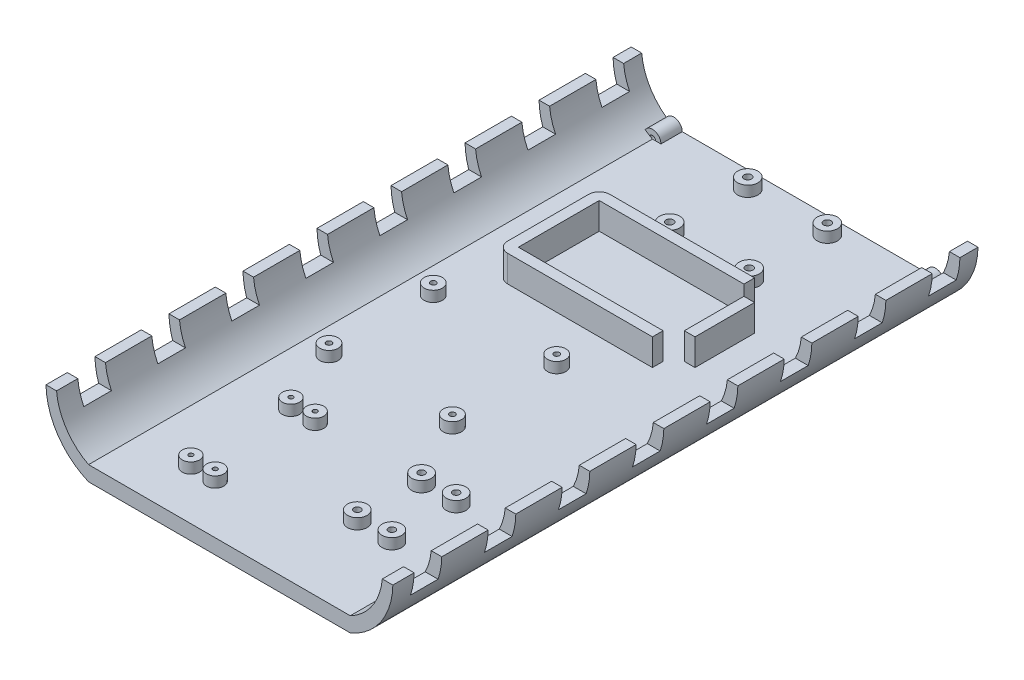
SolidWorks part; units mm, degrees
ref_plane "Front Plane" through (0, 0, 0) normal (0, 0, 1) x (1, 0, 0)
ref_plane "Top Plane" through (0, 0, 0) normal (0, 1, 0) x (1, 0, 0)
ref_plane "Right Plane" through (0, 0, 0) normal (1, 0, 0) x (0, 0, -1)
sketch "Sketch1" plane through (0, 0, 0) normal (0, 1, 0) x (1, 0, 0)
  line L1 (61.5, -137.5) -> (-61.5, -137.5)
  line L2 (61.5, -137.5) -> (61.5, 137.5)
  line L3 (61.5, 137.5) -> (-61.5, 137.5)
  line L4 (-61.5, -137.5) -> (-61.5, 137.5)
  line L5 (61.5, -137.5) -> (-61.5, 137.5) construction
  line L6 (61.5, 137.5) -> (-61.5, -137.5) construction
  point P0 (0, 0)
  dimension "D1" = 123
  dimension "D2" = 275
extrude "Boss-Extrude1" add sketch "Sketch1" along normal blind 7
sketch "Sketch2" plane through (0, 0, 137.5) normal (0, 0, 1) x (1, 0, 0)
  line L0 (-61.5, 7) -> (-76.548, 22.0465) construction
  line L1 (0, 0) -> (0, 29.496) construction
  line L2 (-61.5, 0) -> (-81.498, 19.996) construction
  line L3 (-81.498, 19.996) -> (-81.498, 29.496) construction
  line L4 (-81.498, 29.496) -> (-76.548, 29.496)
  line L5 (-76.548, 29.496) -> (-76.548, 22.0465) construction
  line L6 (-61.5, 0) -> (61.5, 0) construction
  line L7 (-61.5, 7) -> (-61.5, 0)
  line L8 (81.498, 29.496) -> (76.548, 29.496)
  line L9 (61.5, 7) -> (61.5, 0)
  arc A0 (-81.498, 29.496) -> (-61.5, 0) centre (-49.0031, 30) ccw
  arc A1 (-76.548, 29.496) -> (-61.5, 7) centre (-48.4655, 32) ccw
  arc A2 (81.498, 29.496) -> (61.5, 0) centre (49.0031, 30) cw
  arc A3 (76.548, 29.496) -> (61.5, 7) centre (48.4655, 32) cw
  dimension "D1" = 21.28
  dimension "D2" = 4.95
  dimension "D3" = 28.28
  dimension "D4" = 9.5
  dimension "D5" = 30
  dimension "D6" = 32
extrude "Boss-Extrude2" add sketch "Sketch2" against normal up to surface (275 mm away) contours A1 L7 A0 L4 | L8 A3 L9 A2 up to face at (0, 3.5, -137.5)
sketch "Sketch3" plane through (0, 0, 0) normal (1, 0, 0) x (0, 0, -1)
  line L0 (137.5, 29.496) -> (-137.5, 29.496) construction
  line L1 (-127.5, 29.496) -> (-114.5, 29.496)
  line L2 (-127.5, 29.496) -> (-127.5, 19.496)
  line L3 (-127.5, 19.496) -> (-114.5, 19.496)
  line L8 (-92.7143, 29.496) -> (-92.7143, 19.496)
  line L9 (-92.7143, 29.496) -> (-79.7143, 29.496)
  line L10 (-79.7143, 29.496) -> (-79.7143, 19.496)
  line L11 (-92.7143, 19.496) -> (-79.7143, 19.496)
  line L12 (-57.9286, 29.496) -> (-57.9286, 19.496)
  line L13 (-57.9286, 29.496) -> (-44.9286, 29.496)
  line L14 (-44.9286, 29.496) -> (-44.9286, 19.496)
  line L15 (-57.9286, 19.496) -> (-44.9286, 19.496)
  line L16 (-23.1429, 29.496) -> (-23.1429, 19.496)
  line L17 (-23.1429, 29.496) -> (-10.1429, 29.496)
  line L18 (-10.1429, 29.496) -> (-10.1429, 19.496)
  line L19 (-23.1429, 19.496) -> (-10.1429, 19.496)
  line L20 (11.6429, 29.496) -> (11.6429, 19.496)
  line L21 (11.6429, 29.496) -> (24.6429, 29.496)
  line L22 (24.6429, 29.496) -> (24.6429, 19.496)
  line L23 (11.6429, 19.496) -> (24.6429, 19.496)
  line L24 (46.4286, 29.496) -> (46.4286, 19.496)
  line L25 (46.4286, 29.496) -> (59.4286, 29.496)
  line L26 (59.4286, 29.496) -> (59.4286, 19.496)
  line L27 (46.4286, 19.496) -> (59.4286, 19.496)
  line L28 (81.2143, 29.496) -> (81.2143, 19.496)
  line L29 (81.2143, 29.496) -> (94.2143, 29.496)
  line L30 (94.2143, 29.496) -> (94.2143, 19.496)
  line L31 (81.2143, 19.496) -> (94.2143, 19.496)
  line L32 (116, 29.496) -> (116, 19.496)
  line L33 (116, 29.496) -> (129, 29.496)
  line L35 (116, 19.496) -> (129, 19.496)
  line L37 (137.5, 29.496) -> (-137.5, 29.496) construction
  line L38 (-127.5, 38.996) -> (-127.5, 29.496) construction
  line L39 (-114.5, 29.496) -> (-114.5, 19.496)
  line L40 (-114.5, 38.996) -> (-114.5, 29.496) construction
  line L41 (129, 29.496) -> (129, 19.496)
  line L42 (129, 38.996) -> (129, 29.496) construction
  dimension "D1" = 10
  dimension "D2" = 8
extrude "Cut-Extrude1" cut sketch "Sketch3" against normal through all both and the other way through all contours L2 L1 L39 L3 | L8 L11 L10 L9 | L12 L15 L14 L13 | L16 L19 L18 L17 | L20 L23 L22 L21 | L24 L27 L26 L25 | L28 L31 L30 L29 | L32 L35 L41 L33
sketch "Sketch4" plane through (0, 0, -137.5) normal (0, 0, -1) x (-1, 0, 0)
  line L0 (0, 0) -> (0, 7) construction
  line L1 (-61.5, 7) -> (61.5, 7) construction
  circle A0 centre (61.5, 7) radius 1.5
  circle A1 centre (61.5, 7) radius 4
  circle A2 centre (-61.5, 7) radius 4
  circle A3 centre (-61.5, 7) radius 1.5
  dimension "D1" = 3
  dimension "D2" = 8
extrude "Boss-Extrude3" add sketch "Sketch4" against normal blind 10
sketch "Sketch5" plane through (0, 0, -137.5) normal (0, 0, -1) x (-1, 0, 0)
  circle A0 centre (61.5, 7) radius 1.5
  circle A1 centre (-61.5, 7) radius 1.5
  dimension "D1" = 3
  dimension "D2" = 3
extrude "Cut-Extrude2" cut sketch "Sketch5" against normal blind 10
sketch "Sketch8" plane through (0, 0, 0) normal (0, -1, 0) x (1, 0, 0)
  line L0 (-0.0256, 57.4884) -> (-0.0256, -44.5116) construction
  line L1 (-50.0256, -29.5701) -> (49.9744, -29.5701) construction
  arc A0 (-50.0256, -29.5701) -> (-0.0256, 57.4884) centre (39.7518, -23.2442) cw
  arc A1 (-0.0256, 38.2605) -> (-32.6817, -19.623) centre (42.2063, -23.719) ccw
  arc A2 (-0.0256, 38.2605) -> (32.6306, -19.623) centre (-42.2575, -23.719) cw
  arc A3 (49.9744, -29.5701) -> (-0.0256, 57.4884) centre (-39.803, -23.2442) ccw
  arc A4 (-50.0256, -29.5701) -> (49.9744, -29.5701) centre (-0.0256, 45.263) ccw
  arc A5 (-32.6817, -19.623) -> (32.6306, -19.623) centre (-0.0256, 47.763) ccw
  dimension "D3" = 90
  dimension "D4" = 75
  dimension "D9" = 90
  dimension "D1" = 100
  dimension "D2" = 102
  dimension "D5" = 2.5
  dimension "D6" = 87.0586
  dimension "D7" = 57.8835
  dimension "D8" = 82.7721
  dimension "D10" = 2.5
extrude "Cut-Extrude3" cut sketch "Sketch8" against normal blind 3 contours A0 A3 A4 | A1 A5 A2
sketch "Sketch9" plane through (0, 0, 0) normal (0, -1, 0) x (1, 0, 0)
  line L0 (-50.0889, -28.6883) -> (38.178, 22.4605) construction
  line L1 (11.8277, 51.2634) -> (5.8441, 51.7067)
  line L2 (-0.0889, 58.3703) -> (-0.0889, -43.8551) construction
  line L3 (-49.9678, -14.9758) -> (-47.3599, -20.3794)
  line L4 (-44.0439, -15.9285) -> (-49.9678, -14.9758)
  line L5 (-44.0439, -15.9285) -> (-45.6972, -18.1477) construction
  line L6 (-47.3599, -20.3794) -> (-48.837, -22.3621) construction
  line L7 (-47.3599, -20.3794) -> (-50.3006, -19.7443)
  line L8 (-45.4283, -18.6228) -> (-42.7418, -23.3693)
  line L9 (-42.7418, -23.3693) -> (-39.7214, -18.6859) construction
  line L10 (-39.7214, -18.6859) -> (-45.1135, -18.2003)
  line L11 (-49.905, -24.6318) -> (-48.5689, -22.8383)
  line L12 (-42.7418, -23.3693) -> (-43.8348, -25.0642) construction
  line L13 (-45.6931, -27.9456) -> (-48.5689, -22.8383)
  line L14 (-48.2824, -22.4538) -> (-42.7418, -23.3693)
  line L15 (-48.5689, -22.8383) -> (-48.837, -22.3621) construction
  line L16 (-48.837, -22.3621) -> (-50.3056, -24.3333) construction
  line L17 (-48.837, -22.3621) -> (-48.2824, -22.4538) construction
  line L18 (-48.2824, -22.4538) -> (-45.4283, -18.6228)
  line L19 (-48.5689, -22.8383) -> (-48.2824, -22.4538) construction
  line L20 (-45.6972, -18.1477) -> (-47.3599, -20.3794) construction
  line L21 (-45.1135, -18.2003) -> (-45.6972, -18.1477) construction
  line L22 (-45.6972, -18.1477) -> (-45.4283, -18.6228) construction
  line L23 (-45.1135, -18.2003) -> (-43.6305, -16.2097)
  line L24 (-45.4283, -18.6228) -> (-45.1135, -18.2003) construction
  line L25 (-39.2905, -18.9395) -> (-40.7869, -21.2598)
  line L26 (-43.8348, -25.0642) -> (-45.6931, -27.9456) construction
  line L27 (-50.3056, -24.3333) -> (-49.905, -24.6318)
  line L28 (-35.4051, -21.3791) -> (-40.7869, -21.2598)
  line L29 (-41.4061, -21.2461) -> (-41.389, -21.2717)
  line L30 (-36.1561, -23.7758) -> (-34.9595, -21.6011)
  line L31 (-30.7483, -23.5189) -> (-36.1561, -23.7758)
  line L32 (-36.4101, -24.2375) -> (-33.0992, -28.5716)
  line L33 (-30.2812, -23.6993) -> (-31.4515, -26.2144)
  line L34 (-38.713, -28.423) -> (-33.0992, -28.5716)
  line L35 (-38.713, -28.423) -> (-36.4101, -24.2375)
  line L36 (-38.0831, -26.2419) -> (-43.725, -25.8157)
  line L37 (-43.8692, -26.0393) -> (-40.4599, -30.5618)
  line L38 (-40.4599, -30.5618) -> (-40.0223, -30.8026)
  line L39 (-40.0223, -30.8026) -> (-38.9442, -28.8432)
  line L40 (-35.3964, -33.5088) -> (-38.9442, -28.8432)
  line L41 (-2.0353, 58.2366) -> (11.9562, -43.0268) construction
  line L42 (-26.1016, -25.5957) -> (-31.4515, -26.2144)
  line L43 (-31.6852, -26.7168) -> (-28.0912, -30.7796)
  line L44 (-26.5199, -28.0729) -> (-25.6322, -25.7548)
  line L45 (-21.1981, -27.0783) -> (-26.5199, -28.0729)
  line L46 (-26.7083, -28.565) -> (-22.8354, -32.4051)
  line L47 (-20.7105, -27.1924) -> (-21.5257, -29.8447)
  line L48 (-28.4166, -33.0263) -> (-22.8354, -32.4051)
  line L49 (-28.4166, -33.0263) -> (-26.7083, -28.565)
  line L50 (-28.0912, -30.7796) -> (-33.7384, -31.1296)
  line L51 (-33.8501, -31.3698) -> (-29.8544, -35.3841)
  line L52 (-29.8544, -35.3841) -> (-29.3879, -35.5627)
  line L53 (-29.3879, -35.5627) -> (-28.5881, -33.4742)
  line L54 (-24.4352, -37.6103) -> (-28.5881, -33.4742)
  line L55 (-3.945, 57.8378) -> (23.7745, -40.5577) construction
  line L56 (-16.3086, -28.4989) -> (-21.5257, -29.8447)
  line L57 (-21.6885, -30.3743) -> (-17.5723, -33.9069)
  line L58 (-16.3862, -31.0107) -> (-15.8242, -28.5929)
  line L59 (-11.2507, -29.297) -> (-16.3862, -31.0107)
  line L60 (-16.5055, -31.5239) -> (-12.1434, -34.7978)
  line L61 (-10.752, -29.3429) -> (-11.1966, -32.0822)
  line L62 (-17.5872, -36.1771) -> (-12.1434, -34.7978)
  line L63 (-17.5872, -36.1771) -> (-16.5055, -31.5239)
  line L64 (-17.5723, -33.9069) -> (-23.1184, -35.0265)
  line L65 (-23.196, -35.2791) -> (-18.6887, -38.7094)
  line L66 (-18.6887, -38.7094) -> (-18.2021, -38.8225)
  line L67 (-18.2021, -38.8225) -> (-17.6957, -36.6442)
  line L68 (-13.0157, -40.173) -> (-17.6957, -36.6442)
  line L69 (-5.7815, 57.1796) -> (32.331, -30.0564) construction
  line L70 (-6.2106, -30.0342) -> (-11.1966, -32.0822)
  line L71 (-11.2853, -32.6291) -> (-6.7243, -35.5651)
  line L72 (-5.9458, -32.5338) -> (-5.72, -30.0619)
  line L73 (-1.0931, -30.1334) -> (-5.9458, -32.5338)
  line L74 (-5.9937, -33.0586) -> (-1.2246, -35.7046)
  line L75 (-0.5929, -30.1105) -> (-0.6583, -32.885)
  line L76 (-6.4283, -37.816) -> (-1.2246, -35.7046)
  line L77 (-6.4283, -37.816) -> (-5.9937, -33.0586)
  line L78 (-6.7243, -35.5651) -> (-12.065, -37.4333)
  line L79 (-12.1073, -37.6937) -> (-7.1729, -40.4753)
  line L80 (-7.1729, -40.4753) -> (-6.6754, -40.5207)
  line L81 (-6.6754, -40.5207) -> (-6.472, -38.2935)
  line L82 (-1.353, -41.1486) -> (-6.472, -38.2935)
  line L83 (10.3335, -40.5187) -> (10.8273, -40.4403)
  line L84 (4.0023, -30.1727) -> (-0.6583, -32.885)
  line L85 (-0.6714, -33.4389) -> (4.2485, -35.723)
  line L86 (4.6048, -32.6136) -> (4.4902, -30.1341)
  line L87 (9.0833, -29.5716) -> (4.6048, -32.6136)
  line L88 (4.6292, -33.14) -> (9.7156, -35.1084)
  line L89 (9.5757, -29.4807) -> (9.8906, -32.2378)
  line L90 (4.8498, -37.9121) -> (9.7156, -35.1084)
  line L91 (4.8498, -37.9121) -> (4.6292, -33.14)
  line L92 (4.2485, -35.723) -> (-0.7862, -38.3046)
  line L93 (-0.7924, -38.5682) -> (4.4762, -40.6483)
  line L94 (4.4762, -40.6483) -> (4.9752, -40.6252)
  line L95 (4.9752, -40.6252) -> (4.8719, -38.3912)
  line L96 (10.3335, -40.5187) -> (4.8719, -38.3912)
  line L97 (-1.353, -41.1486) -> (-0.8531, -41.1382)
  line L98 (14.1377, -28.912) -> (9.8906, -32.2378)
  line L99 (9.9535, -32.7883) -> (15.1397, -34.3776)
  line L100 (15.0671, -31.2487) -> (14.6142, -28.8082)
  line L101 (19.087, -27.6224) -> (15.0671, -31.2487)
  line L102 (15.1632, -31.7668) -> (20.4712, -33.0205)
  line L103 (19.5625, -27.4655) -> (20.2517, -30.153)
  line L104 (16.0349, -36.4638) -> (20.4712, -33.0205)
  line L105 (16.0349, -36.4638) -> (15.1632, -31.7668)
  line L106 (15.1397, -34.3776) -> (10.5057, -37.6239)
  line L107 (10.5356, -37.8861) -> (16.0394, -39.2254)
  line L108 (16.0394, -39.2254) -> (16.5305, -39.1342)
  line L109 (16.5305, -39.1342) -> (16.1224, -36.9353)
  line L110 (21.8238, -38.2953) -> (16.1224, -36.9353)
  line L111 (-13.0157, -40.173) -> (-12.5191, -40.2312)
  line L112 (24.0048, -26.2759) -> (20.2517, -30.153)
  line L113 (20.3893, -30.6897) -> (25.7442, -31.5541)
  line L114 (25.2441, -28.4646) -> (24.4614, -26.1091)
  line L115 (28.7298, -24.3222) -> (25.2441, -28.4646)
  line L116 (25.4102, -28.9647) -> (30.8398, -29.4801)
  line L117 (29.1797, -24.1026) -> (30.2299, -26.6696)
  line L118 (26.9166, -33.4982) -> (30.8398, -29.4801)
  line L119 (26.9166, -33.4982) -> (25.4102, -28.9647)
  line L120 (25.7442, -31.5541) -> (21.5982, -35.4042)
  line L121 (21.6639, -35.6604) -> (27.2989, -36.2332)
  line L122 (27.2989, -36.2332) -> (27.773, -36.0756)
  line L123 (27.773, -36.0756) -> (27.0678, -33.9533)
  line L124 (31.7808, -34.4113) -> (27.0678, -33.9533)
  line L125 (-24.4352, -37.6103) -> (-23.9513, -37.7364)
  line L126 (32.6776, -23.3255) -> (30.2299, -26.6696)
  line L127 (30.4397, -27.1824) -> (32.5504, -27.2305)
  line L128 (-35.3964, -33.5088) -> (-34.9346, -33.7006)
  line L129 (21.8238, -38.2953) -> (22.3024, -38.1506)
  line L130 (28.7298, -24.3222) -> (29.1797, -24.1026)
  line L131 (24.0048, -26.2759) -> (24.4614, -26.1091)
  line L132 (19.087, -27.6224) -> (19.5625, -27.4655)
  line L133 (14.1377, -28.912) -> (14.6142, -28.8082)
  line L134 (9.0833, -29.5716) -> (9.5757, -29.4807)
  line L135 (4.0023, -30.1727) -> (4.4902, -30.1341)
  line L136 (-1.0931, -30.1334) -> (-0.5929, -30.1105)
  line L137 (-6.2106, -30.0342) -> (-5.72, -30.0619)
  line L138 (-11.2507, -29.297) -> (-10.752, -29.3429)
  line L139 (-16.3086, -28.4989) -> (-15.8242, -28.5929)
  line L140 (-21.1981, -27.0783) -> (-20.7105, -27.1924)
  line L141 (-26.1016, -25.5957) -> (-25.6322, -25.7548)
  line L142 (-30.7483, -23.5189) -> (-30.2812, -23.6993)
  line L143 (-35.4051, -21.3791) -> (-34.9595, -21.6011)
  line L144 (8.0407, 46.6095) -> (11.8277, 51.2634)
  line L145 (5.8441, 51.7067) -> (7.8645, 53.9359)
  line L146 (6.3995, 49.1556) -> (0.9457, 49.2022)
  line L147 (3.4915, 44.2448) -> (6.6081, 48.6717)
  line L148 (3.434, 56.037) -> (4.3191, 53.9832)
  line L149 (-1.5418, 54.0463) -> (4.3191, 53.9832)
  line L150 (4.5089, 53.5428) -> (0.9457, 49.2022)
  line L151 (4.5089, 53.5428) -> (6.3995, 49.1556)
  line L152 (6.6081, 48.6717) -> (7.5905, 46.3921)
  line L153 (3.0564, 43.9984) -> (1.7951, 46.4545)
  line L154 (3.8928, 56.2347) -> (3.434, 56.037)
  line L155 (-0.999, 41.8534) -> (1.7951, 46.4545)
  line L156 (2.1166, 46.9839) -> (2.0859, 46.9819)
  line L157 (-2.6992, 43.7021) -> (-1.4141, 41.5785)
  line L158 (-5.1806, 38.8904) -> (-2.6992, 43.7021)
  line L159 (-2.972, 44.1529) -> (-8.3809, 43.4526)
  line L160 (-5.5704, 38.5761) -> (-7.1634, 40.8471)
  line L161 (-5.4453, 48.24) -> (-8.3809, 43.4526)
  line L162 (-5.4453, 48.24) -> (-2.972, 44.1529)
  line L163 (-3.8714, 46.604) -> (-0.6813, 51.2769)
  line L164 (-0.8028, 51.5136) -> (-6.4241, 50.8223)
  line L165 (-6.4241, 50.8223) -> (-6.8515, 50.5637)
  line L166 (-6.8515, 50.5637) -> (-5.6936, 48.6503)
  line L167 (-11.508, 47.9106) -> (-5.6936, 48.6503)
  line L168 (-9.3025, 35.9046) -> (-7.1634, 40.8471)
  line L169 (-7.4816, 41.3007) -> (-12.797, 40.2196)
  line L170 (-11.2387, 37.5054) -> (-9.675, 35.5777)
  line L171 (-13.0382, 32.3994) -> (-11.2387, 37.5054)
  line L172 (-11.5706, 37.9147) -> (-16.8328, 36.4807)
  line L173 (-13.3808, 32.0341) -> (-15.2701, 34.0663)
  line L174 (-14.5801, 41.6248) -> (-16.8328, 36.4807)
  line L175 (-14.5801, 41.6248) -> (-11.5706, 37.9147)
  line L176 (-12.797, 40.2196) -> (-10.2766, 45.2852)
  line L177 (-10.4287, 45.5021) -> (-15.9031, 44.0488)
  line L178 (-43.8692, -26.0393) -> (-45.2625, -28.1997)
  line L179 (-43.725, -25.8157) -> (-43.8692, -26.0393) construction
  line L180 (-43.725, -25.8157) -> (-44.0566, -25.7907) construction
  line L181 (-44.0566, -25.7907) -> (-43.8692, -26.0393) construction
  line L182 (-41.373, -21.2469) -> (-41.4061, -21.2461)
  line L183 (-40.7869, -21.2598) -> (-41.373, -21.2469) construction
  line L184 (-41.0872, -21.7255) -> (-43.725, -25.8157)
  line L185 (-40.7869, -21.2598) -> (-41.0872, -21.7255) construction
  line L186 (-41.0872, -21.7255) -> (-38.0831, -26.2419)
  line L187 (-41.389, -21.2717) -> (-41.0872, -21.7255) construction
  line L188 (-31.4515, -26.2144) -> (-32.0667, -26.2856) construction
  line L189 (-32.0667, -26.2856) -> (-31.6852, -26.7168) construction
  line L190 (-31.6852, -26.7168) -> (-33.7384, -31.1296)
  line L191 (-31.4515, -26.2144) -> (-31.6852, -26.7168) construction
  line L192 (-34.0688, -31.15) -> (-33.8501, -31.3698) construction
  line L193 (-33.7384, -31.1296) -> (-34.0688, -31.15) construction
  line L194 (-33.8501, -31.3698) -> (-34.9346, -33.7006)
  line L195 (-33.7384, -31.1296) -> (-33.8501, -31.3698) construction
  line L196 (-23.442, -35.0919) -> (-23.196, -35.2791) construction
  line L197 (-23.196, -35.2791) -> (-23.9513, -37.7364)
  line L198 (-23.1184, -35.0265) -> (-23.196, -35.2791) construction
  line L199 (-23.1184, -35.0265) -> (-23.442, -35.0919) construction
  line L200 (-22.1254, -29.9993) -> (-21.6885, -30.3743) construction
  line L201 (-21.5257, -29.8447) -> (-22.1254, -29.9993) construction
  line L202 (-21.6885, -30.3743) -> (-23.1184, -35.0265)
  line L203 (-21.5257, -29.8447) -> (-21.6885, -30.3743) construction
  line L204 (-12.3761, -37.5421) -> (-12.1073, -37.6937) construction
  line L205 (-12.1073, -37.6937) -> (-12.5191, -40.2312)
  line L206 (-12.065, -37.4333) -> (-12.1073, -37.6937) construction
  line L207 (-12.065, -37.4333) -> (-12.3761, -37.5421) construction
  line L208 (-0.0899, 44.1495) -> (0.1587, 48.5959) construction
  line L209 (-11.7694, -32.3175) -> (-11.2853, -32.6291) construction
  line L210 (-11.1966, -32.0822) -> (-11.7694, -32.3175) construction
  line L211 (-11.2853, -32.6291) -> (-12.065, -37.4333)
  line L212 (-11.1966, -32.0822) -> (-11.2853, -32.6291) construction
  line L213 (-0.6583, -32.885) -> (-1.1936, -33.1965) construction
  line L214 (-1.1936, -33.1965) -> (-0.6714, -33.4389) construction
  line L215 (-0.6714, -33.4389) -> (-0.7862, -38.3046)
  line L216 (-0.6583, -32.885) -> (-0.6714, -33.4389) construction
  line L217 (-0.7862, -38.3046) -> (-1.0794, -38.4549) construction
  line L218 (-1.0794, -38.4549) -> (-0.7924, -38.5682) construction
  line L219 (-0.7924, -38.5682) -> (-0.8531, -41.1382)
  line L220 (-0.7862, -38.3046) -> (-0.7924, -38.5682) construction
  line L221 (9.8906, -32.2378) -> (9.403, -32.6196) construction
  line L222 (9.9535, -32.7883) -> (10.5057, -37.6239)
  line L223 (9.8906, -32.2378) -> (9.9535, -32.7883) construction
  line L224 (9.403, -32.6196) -> (9.9535, -32.7883) construction
  line L225 (10.5057, -37.6239) -> (10.2356, -37.8131) construction
  line L226 (10.2356, -37.8131) -> (10.5356, -37.8861) construction
  line L227 (10.5356, -37.8861) -> (10.8273, -40.4403)
  line L228 (10.5057, -37.6239) -> (10.5356, -37.8861) construction
  line L229 (21.356, -35.6291) -> (21.6639, -35.6604) construction
  line L230 (21.5982, -35.4042) -> (21.356, -35.6291) construction
  line L231 (21.6639, -35.6604) -> (22.3024, -38.1506)
  line L232 (21.5982, -35.4042) -> (21.6639, -35.6604) construction
  line L233 (20.2517, -30.153) -> (19.8209, -30.5979) construction
  line L234 (19.8209, -30.5979) -> (20.3893, -30.6897) construction
  line L235 (20.3893, -30.6897) -> (21.5982, -35.4042)
  line L236 (20.2517, -30.153) -> (20.3893, -30.6897) construction
  line L237 (30.2299, -26.6696) -> (29.8641, -27.1693) construction
  line L238 (30.4397, -27.1824) -> (32.1836, -31.4455)
  line L239 (30.2299, -26.6696) -> (30.4397, -27.1824) construction
  line L240 (29.8641, -27.1693) -> (30.4397, -27.1824) construction
  line L241 (-15.9031, 44.0488) -> (-16.291, 43.7341)
  line L242 (-16.291, 43.7341) -> (-14.8822, 41.9972)
  line L243 (-20.5406, 40.4687) -> (-14.8822, 41.9972)
  line L244 (-16.7133, 28.8752) -> (-15.2701, 34.0663)
  line L245 (-15.6474, 34.4721) -> (-20.7649, 32.6736)
  line L246 (-18.8497, 30.1983) -> (-17.0369, 28.5027)
  line L247 (-19.9334, 24.894) -> (-18.8497, 30.1983)
  line L248 (-19.2345, 30.5582) -> (-24.2509, 28.4175)
  line L249 (-20.2224, 24.485) -> (-22.3725, 26.2397)
  line L250 (-22.7235, 33.8216) -> (-24.2509, 28.4175)
  line L251 (-22.7235, 33.8216) -> (-19.2345, 30.5582)
  line L252 (-20.7649, 32.6736) -> (-18.9614, 38.0365)
  line L253 (-19.1413, 38.23) -> (-24.3658, 36.0417)
  line L254 (-24.3658, 36.0417) -> (-24.707, 35.6769)
  line L255 (-24.707, 35.6769) -> (-23.0737, 34.1491)
  line L256 (-28.4697, 31.8605) -> (-23.0737, 34.1491)
  line L257 (-23.0918, 20.8977) -> (-22.3725, 26.2397)
  line L258 (-22.8018, 26.59) -> (-27.6249, 24.1081)
  line L259 (-25.389, 21.9182) -> (-23.3612, 20.4867)
  line L260 (-25.7365, 16.5155) -> (-25.389, 21.9182)
  line L261 (-25.8195, 22.2221) -> (-30.4956, 19.4149)
  line L262 (-25.9668, 16.0708) -> (-28.3368, 17.5147)
  line L263 (-29.7222, 24.9772) -> (-30.4956, 19.4149)
  line L264 (-29.7222, 24.9772) -> (-25.8195, 22.2221)
  line L265 (-27.6249, 24.1081) -> (-26.5725, 29.6674)
  line L266 (-26.7768, 29.8341) -> (-31.6529, 26.9516)
  line L267 (-31.6529, 26.9516) -> (-31.941, 26.5435)
  line L268 (-31.941, 26.5435) -> (-30.114, 25.2538)
  line L269 (-35.146, 22.2481) -> (-30.114, 25.2538)
  line L270 (-40.4437, 11.8124) -> (-40.6228, 11.3455)
  line L271 (-28.3182, 12.1224) -> (-28.3368, 17.5147)
  line L272 (-28.81, 17.803) -> (-33.2481, 14.6843)
  line L273 (-30.7334, 12.821) -> (-28.5288, 11.6805)
  line L274 (-30.3382, 7.4216) -> (-30.7334, 12.821)
  line L275 (-31.2015, 13.0631) -> (-35.4494, 9.6424)
  line L276 (-30.5057, 6.9497) -> (-33.0508, 8.0555)
  line L277 (-35.4445, 15.2581) -> (-35.4494, 9.6424)
  line L278 (-35.4445, 15.2581) -> (-31.2015, 13.0631)
  line L279 (-33.2481, 14.6843) -> (-32.9664, 20.3353)
  line L280 (-33.1916, 20.4724) -> (-37.6273, 16.9498)
  line L281 (-37.6273, 16.9498) -> (-37.8569, 16.5061)
  line L282 (-37.8569, 16.5061) -> (-35.8705, 15.4785)
  line L283 (-40.4437, 11.8124) -> (-35.8705, 15.4785)
  line L284 (-35.146, 22.2481) -> (-35.387, 21.81)
  line L285 (-32.2941, 2.7145) -> (-33.0508, 8.0555)
  line L286 (-33.559, 8.2763) -> (-37.5285, 4.5795)
  line L287 (-34.7825, 3.078) -> (-32.4425, 2.2499)
  line L288 (-33.6519, -2.2166) -> (-34.7825, 3.078)
  line L289 (-35.2792, 3.2537) -> (-39.019, -0.7162)
  line L290 (-33.7538, -2.7068) -> (-36.4258, -1.9599)
  line L291 (-39.7828, 4.8473) -> (-39.019, -0.7162)
  line L292 (-39.7828, 4.8473) -> (-35.2792, 3.2537)
  line L293 (-37.5285, 4.5795) -> (-38.0229, 10.2159)
  line L294 (-38.2649, 10.321) -> (-42.1766, 6.2243)
  line L295 (-42.1766, 6.2243) -> (-42.3432, 5.7534)
  line L296 (-42.3432, 5.7534) -> (-40.2349, 5.0073)
  line L297 (-44.2634, 0.7498) -> (-40.2349, 5.0073)
  line L298 (-28.4697, 31.8605) -> (-28.7685, 31.4596)
  line L299 (-34.9447, -7.1487) -> (-36.4258, -1.9599)
  line L300 (-36.9594, -1.8107) -> (-40.3856, -6.016)
  line L301 (-37.4599, -7.1276) -> (-35.0286, -7.6275)
  line L302 (-35.6154, -12.2176) -> (-37.4599, -7.1276)
  line L303 (-37.976, -7.0215) -> (-41.1372, -11.4659)
  line L304 (-35.6501, -12.717) -> (-38.3983, -12.3429)
  line L305 (-42.6554, -6.0592) -> (-41.1372, -11.4659)
  line L306 (-42.6554, -6.0592) -> (-37.976, -7.0215)
  line L307 (-40.3856, -6.016) -> (-41.6468, -0.5004)
  line L308 (-41.9015, -0.4292) -> (-45.2151, -5.0229)
  line L309 (-45.2151, -5.0229) -> (-45.3157, -5.5122)
  line L310 (-45.3157, -5.5122) -> (-43.1251, -5.9627)
  line L311 (-45.8782, -9.8152) -> (-43.1251, -5.9627)
  line L312 (-20.5406, 40.4687) -> (-20.8918, 40.1127)
  line L313 (-36.726, -16.1348) -> (-38.3983, -12.3429)
  line L314 (-38.9473, -12.2682) -> (-40.0443, -14.0722)
  line L315 (-11.508, 47.9106) -> (-11.905, 47.6067)
  line L316 (-44.2634, 0.7498) -> (-44.3774, 0.263)
  line L317 (-35.6154, -12.2176) -> (-35.6501, -12.717)
  line L318 (-34.9447, -7.1487) -> (-35.0286, -7.6275)
  line L319 (-33.6519, -2.2166) -> (-33.7538, -2.7068)
  line L320 (-32.2941, 2.7145) -> (-32.4425, 2.2499)
  line L321 (-30.3382, 7.4216) -> (-30.5057, 6.9497)
  line L322 (-28.3182, 12.1224) -> (-28.5288, 11.6805)
  line L323 (-25.7365, 16.5155) -> (-25.9668, 16.0708)
  line L324 (-23.0918, 20.8977) -> (-23.3612, 20.4867)
  line L325 (-19.9334, 24.894) -> (-20.2224, 24.485)
  line L326 (-16.7133, 28.8752) -> (-17.0369, 28.5027)
  line L327 (-13.0382, 32.3994) -> (-13.3808, 32.0341)
  line L328 (-9.3025, 35.9046) -> (-9.675, 35.5777)
  line L329 (-5.1806, 38.8904) -> (-5.5704, 38.5761)
  line L330 (-0.999, 41.8534) -> (-1.4141, 41.5785)
  line L331 (-0.8028, 51.5136) -> (-1.9772, 53.8004)
  line L332 (2.0994, 46.9556) -> (2.1166, 46.9839)
  line L333 (1.542, 46.9474) -> (-0.6813, 51.2769)
  line L334 (1.542, 46.9474) -> (-3.8714, 46.604)
  line L335 (-7.4816, 41.3007) -> (-10.2766, 45.2852)
  line L336 (-10.4287, 45.5021) -> (-11.905, 47.6067)
  line L337 (-19.1413, 38.23) -> (-20.8918, 40.1127)
  line L338 (-15.6474, 34.4721) -> (-18.9614, 38.0365)
  line L339 (-26.7768, 29.8341) -> (-28.7685, 31.4596)
  line L340 (-22.8018, 26.59) -> (-26.5725, 29.6674)
  line L341 (-28.81, 17.803) -> (-32.9664, 20.3353)
  line L342 (-33.1916, 20.4724) -> (-35.387, 21.81)
  line L343 (-33.559, 8.2763) -> (-38.0229, 10.2159)
  line L344 (-38.2649, 10.321) -> (-40.6228, 11.3455)
  line L345 (-41.9015, -0.4292) -> (-44.3774, 0.263)
  line L346 (-36.9594, -1.8107) -> (-41.6468, -0.5004)
  line L347 (-38.9473, -12.2682) -> (-43.5111, -11.647)
  line L348 (8.0407, 46.6095) -> (6.9455, 49.1509) construction
  line L349 (5.8441, 51.7067) -> (4.8656, 53.9773) construction
  line L350 (0.9457, 49.2022) -> (3.4915, 44.2448) construction
  line L351 (0.9457, 49.2022) -> (0.0244, 50.9962) construction
  line L352 (4.3191, 53.9832) -> (4.8656, 53.9773) construction
  line L353 (4.8656, 53.9773) -> (3.8928, 56.2347) construction
  line L354 (4.8656, 53.9773) -> (4.5089, 53.5428) construction
  line L355 (4.3191, 53.9832) -> (4.5089, 53.5428) construction
  line L356 (6.9455, 49.1509) -> (5.8441, 51.7067) construction
  line L357 (6.6081, 48.6717) -> (6.9455, 49.1509) construction
  line L358 (6.9455, 49.1509) -> (6.3995, 49.1556) construction
  line L359 (6.3995, 49.1556) -> (6.6081, 48.6717) construction
  line L360 (0.0244, 50.9962) -> (-1.5418, 54.0463) construction
  line L361 (-0.6813, 51.2769) -> (-0.8028, 51.5136) construction
  line L362 (-0.6813, 51.2769) -> (-0.4938, 51.5516) construction
  line L363 (-0.4938, 51.5516) -> (-0.8028, 51.5136) construction
  line L364 (1.7951, 46.4545) -> (2.0994, 46.9556) construction
  line L365 (1.7951, 46.4545) -> (1.542, 46.9474) construction
  line L366 (2.0859, 46.9819) -> (1.542, 46.9474) construction
  line L367 (-7.1634, 40.8471) -> (-6.9174, 41.4154) construction
  line L368 (-6.9174, 41.4154) -> (-7.4816, 41.3007) construction
  line L369 (-7.1634, 40.8471) -> (-7.4816, 41.3007) construction
  line L370 (-10.1291, 45.5816) -> (-10.4287, 45.5021) construction
  line L371 (-10.2766, 45.2852) -> (-10.1291, 45.5816) construction
  line L372 (-10.2766, 45.2852) -> (-10.4287, 45.5021) construction
  line L373 (-18.8562, 38.3494) -> (-19.1413, 38.23) construction
  line L374 (-18.9614, 38.0365) -> (-19.1413, 38.23) construction
  line L375 (-18.9614, 38.0365) -> (-18.8562, 38.3494) construction
  line L376 (-15.1043, 34.6629) -> (-15.6474, 34.4721) construction
  line L377 (-15.2701, 34.0663) -> (-15.1043, 34.6629) construction
  line L378 (-15.2701, 34.0663) -> (-15.6474, 34.4721) construction
  line L379 (-26.5112, 29.9912) -> (-26.7768, 29.8341) construction
  line L380 (-26.5725, 29.6674) -> (-26.7768, 29.8341) construction
  line L381 (-26.5725, 29.6674) -> (-26.5112, 29.9912) construction
  line L382 (-22.2898, 26.8535) -> (-22.8018, 26.59) construction
  line L383 (-22.3725, 26.2397) -> (-22.2898, 26.8535) construction
  line L384 (-22.3725, 26.2397) -> (-22.8018, 26.59) construction
  line L385 (-28.3368, 17.5147) -> (-28.339, 18.134) construction
  line L386 (-28.339, 18.134) -> (-28.81, 17.803) construction
  line L387 (-28.3368, 17.5147) -> (-28.81, 17.803) construction
  line L388 (-32.9664, 20.3353) -> (-32.95, 20.6643) construction
  line L389 (-32.95, 20.6643) -> (-33.1916, 20.4724) construction
  line L390 (-32.9664, 20.3353) -> (-33.1916, 20.4724) construction
  line L391 (-33.0508, 8.0555) -> (-33.1377, 8.6687) construction
  line L392 (-33.0508, 8.0555) -> (-33.559, 8.2763) construction
  line L393 (-33.1377, 8.6687) -> (-33.559, 8.2763) construction
  line L394 (-38.0229, 10.2159) -> (-38.0517, 10.5444) construction
  line L395 (-38.0517, 10.5444) -> (-38.2649, 10.321) construction
  line L396 (-38.0229, 10.2159) -> (-38.2649, 10.321) construction
  line L397 (-41.7204, -0.1782) -> (-41.9015, -0.4292) construction
  line L398 (-41.6468, -0.5004) -> (-41.7204, -0.1782) construction
  line L399 (-41.6468, -0.5004) -> (-41.9015, -0.4292) construction
  line L400 (-36.4258, -1.9599) -> (-36.5958, -1.3644) construction
  line L401 (-36.5958, -1.3644) -> (-36.9594, -1.8107) construction
  line L402 (-36.4258, -1.9599) -> (-36.9594, -1.8107) construction
  line L403 (-38.3983, -12.3429) -> (-38.6482, -11.7763) construction
  line L404 (-38.3983, -12.3429) -> (-38.9473, -12.2682) construction
  line L405 (-38.6482, -11.7763) -> (-38.9473, -12.2682) construction
  line L406 (38.2948, -35.3727) -> (41.6705, -30.4124)
  line L407 (36.1579, -29.7661) -> (38.2948, -35.3727)
  line L408 (41.6705, -30.4124) -> (42.5909, -33.2767)
  line L409 (39.1834, -29.6179) -> (41.9507, -24.918)
  line L410 (36.3847, -24.644) -> (38.6601, -29.5565)
  line L411 (46.6257, -30.4903) -> (44.4045, -30.2299)
  line L412 (47.3896, -25.1858) -> (44.4045, -30.2299)
  line L413 (43.9282, -30.1741) -> (41.9507, -24.918)
  line L414 (43.9282, -30.1741) -> (39.1834, -29.6179)
  line L415 (38.6601, -29.5565) -> (36.1948, -29.2675)
  line L416 (36.3888, -24.144) -> (39.1465, -24.2798)
  line L417 (46.5675, -30.9865) -> (46.6257, -30.4903)
  line L418 (36.5588, -19.5594) -> (39.1465, -24.2798)
  line L419 (39.4442, -24.8228) -> (39.4578, -24.7953)
  line L420 (39.0099, -19.0114) -> (36.5283, -19.0625)
  line L421 (36.0836, -14.4566) -> (39.0099, -19.0114)
  line L422 (39.5368, -19.0005) -> (41.6347, -13.9662)
  line L423 (36.0063, -13.9619) -> (38.7695, -13.7178)
  line L424 (44.313, -18.9021) -> (41.6347, -13.9662)
  line L425 (44.313, -18.9021) -> (39.5368, -19.0005)
  line L426 (42.1092, -19.4472) -> (44.561, -24.5463)
  line L427 (44.8267, -24.5594) -> (47.0387, -19.3456)
  line L428 (47.0387, -19.3456) -> (47.0284, -18.8462)
  line L429 (47.0284, -18.8462) -> (44.7924, -18.8923)
  line L430 (47.0591, -13.487) -> (44.7924, -18.8923)
  line L431 (35.5587, -9.394) -> (38.7695, -13.7178)
  line L432 (39.3215, -13.669) -> (41.0429, -8.5251)
  line L433 (37.9132, -8.5176) -> (35.4619, -8.9079)
  line L434 (34.391, -4.4062) -> (37.9132, -8.5176)
  line L435 (38.4336, -8.4348) -> (39.8228, -3.1606)
  line L436 (34.246, -3.9269) -> (36.9506, -3.3067)
  line L437 (43.1514, -7.6836) -> (39.8228, -3.1606)
  line L438 (43.1514, -7.6836) -> (38.4336, -8.4348)
  line L439 (41.0429, -8.5251) -> (44.1696, -13.2407)
  line L440 (44.4335, -13.2174) -> (45.9122, -7.7498)
  line L441 (45.9122, -7.7498) -> (45.8336, -7.2565)
  line L442 (45.8336, -7.2565) -> (43.625, -7.6082)
  line L443 (45.1305, -1.9435) -> (43.625, -7.6082)
  line L444 (33.1765, 0.5386) -> (36.9506, -3.3067)
  line L445 (37.4906, -3.1829) -> (38.4919, 2.1482)
  line L446 (35.3906, 1.7273) -> (33.0157, 1.0051)
  line L447 (31.3387, 5.3179) -> (35.3906, 1.7273)
  line L448 (35.8947, 1.8806) -> (36.549, 7.2952)
  line L449 (31.1291, 5.7727) -> (33.7237, 6.7574)
  line L450 (40.4653, 3.2704) -> (36.549, 7.2952)
  line L451 (40.4653, 3.2704) -> (35.8947, 1.8806)
  line L452 (38.4919, 2.1482) -> (42.2345, -2.0951)
  line L453 (42.492, -2.036) -> (43.2091, 3.5826)
  line L454 (43.2091, 3.5826) -> (43.0638, 4.0606)
  line L455 (43.0638, 4.0606) -> (40.9241, 3.4099)
  line L456 (41.6401, 9.2273) -> (40.9241, 3.4099)
  line L457 (29.4571, 10.0514) -> (33.7237, 6.7574)
  line L458 (34.2418, 6.954) -> (34.5039, 12.3719)
  line L459 (31.4894, 11.5305) -> (29.2358, 10.4901)
  line L460 (26.9843, 14.5328) -> (31.4894, 11.5305)
  line L461 (31.9679, 11.7514) -> (31.8748, 17.2046)
  line L462 (26.7143, 14.9546) -> (29.1498, 16.2851)
  line L463 (36.3052, 13.7537) -> (31.8748, 17.2046)
  line L464 (36.3052, 13.7537) -> (31.9679, 11.7514)
  line L465 (34.5039, 12.3719) -> (38.7921, 8.6809)
  line L466 (39.0387, 8.7744) -> (38.9805, 14.4385)
  line L467 (38.9805, 14.4385) -> (38.7711, 14.8921)
  line L468 (38.7711, 14.8921) -> (36.7406, 13.9547)
  line L469 (36.6537, 19.8153) -> (36.7406, 13.9547)
  line L470 (30.265, 29.6212) -> (29.9501, 30.0097)
  line L471 (24.4706, 18.9652) -> (29.1498, 16.2851)
  line L472 (29.6361, 16.5508) -> (29.1542, 21.9536)
  line L473 (26.2833, 20.7075) -> (24.1932, 19.3685)
  line L474 (21.4096, 23.065) -> (26.2833, 20.7075)
  line L475 (26.727, 20.9918) -> (25.8885, 26.381)
  line L476 (21.0846, 23.446) -> (23.3149, 25.0972)
  line L477 (30.7494, 23.5689) -> (25.8885, 26.381)
  line L478 (30.7494, 23.5689) -> (26.727, 20.9918)
  line L479 (29.1542, 21.9536) -> (33.9073, 18.8842)
  line L480 (34.1387, 19.0106) -> (33.3058, 24.6135)
  line L481 (33.3058, 24.6135) -> (33.0363, 25.0341)
  line L482 (33.0363, 25.0341) -> (31.1532, 23.8276)
  line L483 (30.265, 29.6212) -> (31.1532, 23.8276)
  line L484 (36.6537, 19.8153) -> (36.3947, 20.2431)
  line L485 (18.3111, 27.1124) -> (23.3149, 25.0972)
  line L486 (23.7602, 25.4269) -> (22.5435, 30.7129)
  line L487 (19.8701, 29.0856) -> (17.983, 27.4731)
  line L488 (14.7196, 30.7538) -> (19.8701, 29.0856)
  line L489 (20.2707, 29.4279) -> (18.7024, 34.6516)
  line L490 (14.346, 31.0872) -> (16.3288, 33.0277)
  line L491 (23.9026, 32.5314) -> (18.7024, 34.6516)
  line L492 (23.9026, 32.5314) -> (20.2707, 29.4279)
  line L493 (22.5435, 30.7129) -> (27.6719, 28.323)
  line L494 (27.884, 28.48) -> (26.2919, 33.916)
  line L495 (26.2919, 33.916) -> (25.9674, 34.2957)
  line L496 (25.9674, 34.2957) -> (24.2671, 32.8429)
  line L497 (22.5943, 38.4604) -> (24.2671, 32.8429)
  line L498 (41.6401, 9.2273) -> (41.4423, 9.6866)
  line L499 (11.0946, 34.3395) -> (16.3288, 33.0277)
  line L500 (16.7248, 33.4153) -> (14.796, 38.485)
  line L501 (12.3705, 36.5071) -> (10.7219, 34.6515)
  line L502 (7.0402, 37.4547) -> (12.3705, 36.5071)
  line L503 (12.7205, 36.901) -> (10.4521, 41.8609)
  line L504 (6.625, 37.7345) -> (8.3231, 39.9274)
  line L505 (15.8934, 40.4723) -> (10.4521, 41.8609)
  line L506 (15.8934, 40.4723) -> (12.7205, 36.901)
  line L507 (14.796, 38.485) -> (20.2033, 36.8194)
  line L508 (20.3923, 37.0044) -> (18.0708, 42.171)
  line L509 (18.0708, 42.171) -> (17.6974, 42.5027)
  line L510 (17.6974, 42.5027) -> (16.212, 40.8308)
  line L511 (14.2521, 45.1414) -> (16.212, 40.8308)
  line L512 (45.1305, -1.9435) -> (44.9978, -1.4614)
  line L513 (4.2031, 40.3752) -> (8.3231, 39.9274)
  line L514 (8.6623, 40.3655) -> (7.6485, 42.2175)
  line L515 (47.0591, -13.487) -> (46.9943, -12.9912)
  line L516 (22.5943, 38.4604) -> (22.2296, 38.8025)
  line L517 (7.0402, 37.4547) -> (6.625, 37.7345)
  line L518 (11.0946, 34.3395) -> (10.7219, 34.6515)
  line L519 (14.7196, 30.7538) -> (14.346, 31.0872)
  line L520 (18.3111, 27.1124) -> (17.983, 27.4731)
  line L521 (21.4096, 23.065) -> (21.0846, 23.446)
  line L522 (24.4706, 18.9652) -> (24.1932, 19.3685)
  line L523 (26.9843, 14.5328) -> (26.7143, 14.9546)
  line L524 (29.4571, 10.0514) -> (29.2358, 10.4901)
  line L525 (31.3387, 5.3179) -> (31.1291, 5.7727)
  line L526 (33.1765, 0.5386) -> (33.0157, 1.0051)
  line L527 (34.391, -4.4062) -> (34.246, -3.9269)
  line L528 (35.5587, -9.394) -> (35.4619, -8.9079)
  line L529 (36.0836, -14.4566) -> (36.0063, -13.9619)
  line L530 (36.5588, -19.5594) -> (36.5283, -19.0625)
  line L531 (44.8267, -24.5594) -> (47.3944, -24.6858)
  line L532 (39.4283, -24.7938) -> (39.4442, -24.8228)
  line L533 (39.6999, -24.307) -> (44.561, -24.5463)
  line L534 (39.6999, -24.307) -> (42.1092, -19.4472)
  line L535 (39.3215, -13.669) -> (44.1696, -13.2407)
  line L536 (44.4335, -13.2174) -> (46.9943, -12.9912)
  line L537 (42.492, -2.036) -> (44.9978, -1.4614)
  line L538 (37.4906, -3.1829) -> (42.2345, -2.0951)
  line L539 (39.0387, 8.7744) -> (41.4423, 9.6866)
  line L540 (34.2418, 6.954) -> (38.7921, 8.6809)
  line L541 (29.6361, 16.5508) -> (33.9073, 18.8842)
  line L542 (34.1387, 19.0106) -> (36.3947, 20.2431)
  line L543 (23.7602, 25.4269) -> (27.6719, 28.323)
  line L544 (27.884, 28.48) -> (29.9501, 30.0097)
  line L545 (20.3923, 37.0044) -> (22.2296, 38.8025)
  line L546 (16.7248, 33.4153) -> (20.2033, 36.8194)
  line L547 (8.6623, 40.3655) -> (11.4822, 44.0073)
  line L548 (36.1579, -29.7661) -> (38.9064, -30.0883) construction
  line L549 (41.6705, -30.4124) -> (44.1261, -30.7003) construction
  line L550 (41.9507, -24.918) -> (36.3847, -24.644) construction
  line L551 (41.9507, -24.918) -> (43.965, -25.0172) construction
  line L552 (44.4045, -30.2299) -> (44.1261, -30.7003) construction
  line L553 (44.1261, -30.7003) -> (46.5675, -30.9865) construction
  line L554 (44.1261, -30.7003) -> (43.9282, -30.1741) construction
  line L555 (44.4045, -30.2299) -> (43.9282, -30.1741) construction
  line L556 (38.9064, -30.0883) -> (41.6705, -30.4124) construction
  line L557 (38.6601, -29.5565) -> (38.9064, -30.0883) construction
  line L558 (38.9064, -30.0883) -> (39.1834, -29.6179) construction
  line L559 (39.1834, -29.6179) -> (38.6601, -29.5565) construction
  line L560 (43.965, -25.0172) -> (47.3896, -25.1858) construction
  line L561 (44.561, -24.5463) -> (44.8267, -24.5594) construction
  line L562 (44.561, -24.5463) -> (44.7051, -24.846) construction
  line L563 (44.7051, -24.846) -> (44.8267, -24.5594) construction
  line L564 (39.1465, -24.2798) -> (39.4283, -24.7938) construction
  line L565 (39.1465, -24.2798) -> (39.6999, -24.307) construction
  line L566 (39.4578, -24.7953) -> (39.6999, -24.307) construction
  line L567 (38.7695, -13.7178) -> (39.1388, -14.215) construction
  line L568 (39.1388, -14.215) -> (39.3215, -13.669) construction
  line L569 (38.7695, -13.7178) -> (39.3215, -13.669) construction
  line L570 (44.3526, -13.5167) -> (44.4335, -13.2174) construction
  line L571 (44.1696, -13.2407) -> (44.3526, -13.5167) construction
  line L572 (44.1696, -13.2407) -> (44.4335, -13.2174) construction
  line L573 (42.4529, -2.3426) -> (42.492, -2.036) construction
  line L574 (42.2345, -2.0951) -> (42.492, -2.036) construction
  line L575 (42.2345, -2.0951) -> (42.4529, -2.3426) construction
  line L576 (37.3843, -3.7487) -> (37.4906, -3.1829) construction
  line L577 (36.9506, -3.3067) -> (37.3843, -3.7487) construction
  line L578 (36.9506, -3.3067) -> (37.4906, -3.1829) construction
  line L579 (39.0419, 8.4659) -> (39.0387, 8.7744) construction
  line L580 (38.7921, 8.6809) -> (39.0387, 8.7744) construction
  line L581 (38.7921, 8.6809) -> (39.0419, 8.4659) construction
  line L582 (34.2139, 6.3789) -> (34.2418, 6.954) construction
  line L583 (33.7237, 6.7574) -> (34.2139, 6.3789) construction
  line L584 (33.7237, 6.7574) -> (34.2418, 6.954) construction
  line L585 (29.1498, 16.2851) -> (29.6872, 15.9773) construction
  line L586 (29.6872, 15.9773) -> (29.6361, 16.5508) construction
  line L587 (29.1498, 16.2851) -> (29.6361, 16.5508) construction
  line L588 (33.9073, 18.8842) -> (34.184, 18.7055) construction
  line L589 (34.184, 18.7055) -> (34.1387, 19.0106) construction
  line L590 (33.9073, 18.8842) -> (34.1387, 19.0106) construction
  line L591 (23.3149, 25.0972) -> (23.8894, 24.8659) construction
  line L592 (23.3149, 25.0972) -> (23.7602, 25.4269) construction
  line L593 (23.8894, 24.8659) -> (23.7602, 25.4269) construction
  line L594 (27.6719, 28.323) -> (27.9708, 28.1837) construction
  line L595 (27.9708, 28.1837) -> (27.884, 28.48) construction
  line L596 (27.6719, 28.323) -> (27.884, 28.48) construction
  line L597 (20.5192, 36.7221) -> (20.3923, 37.0044) construction
  line L598 (20.2033, 36.8194) -> (20.5192, 36.7221) construction
  line L599 (20.2033, 36.8194) -> (20.3923, 37.0044) construction
  line L600 (16.3288, 33.0277) -> (16.9296, 32.8772) construction
  line L601 (16.9296, 32.8772) -> (16.7248, 33.4153) construction
  line L602 (16.3288, 33.0277) -> (16.7248, 33.4153) construction
  line L603 (8.3231, 39.9274) -> (8.9387, 39.8605) construction
  line L604 (8.3231, 39.9274) -> (8.6623, 40.3655) construction
  line L605 (8.9387, 39.8605) -> (8.6623, 40.3655) construction
  line L606 (0.0516, 0.305) -> (4.6858, -22.0983) construction
  line L607 (3.8928, 56.2347) -> (7.8645, 53.9359)
  line L608 (-43.5111, -11.647) -> (-44.7429, -11.4659)
  line L609 (-45.8782, -9.8152) -> (-46.2629, -10.3064)
  line L610 (-40.0443, -14.0722) -> (-40.323, -14.5097)
  line L611 (-36.726, -16.1348) -> (-36.4101, -16.8384)
  line L612 (4.2031, 40.3752) -> (2.0994, 40.5782)
  line L613 (7.6485, 42.2175) -> (7.0086, 43.4243)
  line L614 (11.4822, 44.0073) -> (13.3458, 46.414)
  line L615 (14.2521, 45.1414) -> (13.6743, 46.5497)
  arc A0 (32.5673, -18.7411) -> (-49.1466, -7.9292) centre (-0.0889, 48.6449) cw
  arc A1 (-44.0439, -15.9285) -> (-43.6305, -16.2097) centre (0.1587, 48.5959) ccw
  arc A2 (8.0407, 46.6095) -> (7.5905, 46.3921) centre (41.8191, -23.9333) ccw
  arc A3 (-45.6931, -27.9456) -> (-45.2625, -28.1997) centre (-0.1962, 48.6458) ccw
  arc A4 (-39.7214, -18.6859) -> (-39.2905, -18.9395) centre (0.1587, 48.5959) ccw
  arc A5 (-0.0889, 39.1424) -> (31.0702, -38.2892) centre (-42.3208, -22.8371) cw
  arc A6 (-50.2196, -18.2975) -> (32.4703, -28.4311) centre (-0.2026, 47.3992) ccw construction
  arc A7 (-49.6726, -11.6578) -> (-50.2196, -18.2975) centre (203.7167, -35.8761) ccw
  arc A8 (-50.2196, -18.2975) -> (-50.3056, -24.3333) centre (4.6858, -22.0983) ccw
  circle A9 centre (-0.0889, 0.2857) radius 2.8444
  arc A10 (-1.5418, 54.0463) -> (-1.9772, 53.8004) centre (42.0399, -23.6509) ccw
  arc A11 (3.4915, 44.2448) -> (3.0564, 43.9984) centre (41.8191, -23.9333) ccw
  arc A12 (-0.0889, 39.1424) -> (16.6351, 47.6919) centre (42.143, -22.8371) cw
  arc A13 (9.077, 53.1423) -> (-41.044, -13.4025) centre (40.9634, -23.0221) ccw construction
  arc A14 (36.1579, -29.7661) -> (36.1948, -29.2675) centre (-41.8232, -23.7477) ccw
  arc A15 (47.3896, -25.1858) -> (47.3944, -24.6858) centre (-41.689, -24.08) ccw
  arc A16 (36.3847, -24.644) -> (36.3888, -24.144) centre (-41.8232, -23.7477) ccw
  arc A17 (35.2737, -36.776) -> (41.2973, -33.9299) centre (-70.4473, 194.7747) ccw
  arc A18 (41.2973, -33.9299) -> (46.5675, -30.9865) centre (17.1362, 15.52) ccw
  arc A19 (41.2973, -33.9299) -> (8.7284, 42.7485) centre (-40.6062, -23.4622) ccw construction
  arc M1 (-0.0256, 57.4884) -> (49.9744, -29.5701) centre (-39.803, -23.2442) cw
  arc M3 (-50.0256, -29.5701) -> (-0.0256, 57.4884) centre (39.7518, -23.2442) cw
  dimension "D4" = 78.2129
  dimension "D1" = 1.2509
  dimension "D2" = 1.25
  dimension "D3" = 1.25
  dimension "D5" = 6
  dimension "D6" = 6
  dimension "D7" = 6
  dimension "D8" = 6
  dimension "D9" = 0.5
  dimension "D10" = 0.5
  dimension "D11" = 4.4533
  dimension "D12" = 22.8775
extrude "Boss-Extrude5" add sketch "Sketch9" against normal blind 3 separate body contours A5 L126 L117 L130 L115 L114 L131 L112 L103 L132 L101 L100 L133 L98 L89 L134 L87 L86 L135 L84 L75 L136 L73 L72 L137 L70 L61 L138 L59 L58 L139 L56 L47 L140 L45 L44 L141 L42 L33 L142 L31 L30 L143 L28 L25 A4 L10 L23 A1 L4 M3 | A11 L147 L152 A2 L144 L1 L145 L148 L149 A10 L331 L164 L165 L166 L167 L315 L336 L177 L241 L242 L243 L312 L337 L253 L254 L255 L256 L298 L339 L266 L267 L268 L269 L284 L342 L280 L281 L282 L283 L270 L344 L294 L295 L296 L297 L316 L345 L308 L309 M1 | L408 A18 L417 L411 L412 A15 L531 L427 L428 L429 L430 L515 L536 L440 L441 L442 L443 L512 L537 L453 L454 L455 L456 L498 L539 L466 L467 L468 L469 L484 L542 L480 L481 L482 L483 L470 L544 L494 L495 L496 L497 L516 L545 L508 L509 L510 region at (10.457, 0, 50.2959) region at (13.0971, 0, 45.4902) region at (-47.0945, 0, -16.3186)
sketch "Sketch10" plane through (0, 0, 0) normal (0, -1, 0) x (1, 0, 0)
  line L0 (0, 26.8606) -> (0, 2.3606) construction
  line L1 (25, -23.1394) -> (-25, -23.1394)
  line L2 (25, -23.1394) -> (25, 26.8606)
  line L3 (25, 26.8606) -> (-25, 26.8606)
  line L4 (-25, -23.1394) -> (-25, 26.8606)
  line L5 (25, -23.1394) -> (-25, 26.8606) construction
  line L6 (25, 26.8606) -> (0.3536, 2.2142) construction
  line L7 (-25, 1.8606) -> (25, 1.8606) construction
  line L8 (-25, 1.8606) -> (-4.9497, 6.8104)
  line L9 (-4.9497, 6.8104) -> (0, 26.8606)
  line L10 (0, 24.8606) -> (0, 2.3606)
  line L11 (0, -23.1394) -> (-4.9497, -3.0891)
  line L12 (-4.9497, -3.0891) -> (-25, 1.8606)
  line L13 (0, -23.1394) -> (4.9497, -3.0891)
  line L14 (4.9497, 6.8104) -> (0, 26.8606)
  line L15 (25, 1.8606) -> (4.9497, 6.8104)
  line L16 (4.9497, -3.0891) -> (25, 1.8606)
  line L17 (-4.2426, 6.1033) -> (-0.3536, 2.2142)
  line L18 (0.3536, 1.5071) -> (4.2426, -2.382)
  line L19 (4.2426, 6.1033) -> (0.3536, 2.2142)
  line L20 (-4.2426, -2.382) -> (-0.3536, 1.5071)
  line L21 (0, 24.8606) -> (4.2426, 6.1033)
  line L22 (-23, 1.8606) -> (-0.5, 1.8606)
  line L23 (23, 1.8606) -> (4.2426, -2.382)
  line L24 (0, -21.1394) -> (-4.2426, -2.382)
  line L25 (-23, 1.8606) -> (-4.2426, 6.1033)
  line L26 (0, 1.3606) -> (0, -21.1394)
  line L27 (0.5, 1.8606) -> (23, 1.8606)
  line L28 (0, 1.8606) -> (-25, -23.1394) construction
  line L29 (0, 1.8606) -> (0, -23.1394) construction
  arc A0 (-0.3536, 2.2142) -> (-0.5, 1.8606) centre (0, 1.8606) ccw
  arc A1 (0.3536, 2.2142) -> (0, 2.3606) centre (0, 1.8606) ccw
  arc A2 (0.3536, 1.5071) -> (0.5, 1.8606) centre (0, 1.8606) ccw
  arc A3 (-0.3536, 1.5071) -> (0, 1.3606) centre (0, 1.8606) ccw
  point P0 (0, 1.8606)
  dimension "D12" = 1
  dimension "D1" = 50
  dimension "D2" = 50
  dimension "D3" = 7
  dimension "D4" = 2
  dimension "D5" = 1
  dimension "D6" = 2
  dimension "D7" = 1
  dimension "D8" = 1
  dimension "D9" = 2
  dimension "D10" = 1
  dimension "D11" = 2
extrude "Cut-Extrude4" cut sketch "Sketch10" against normal blind 3 contours L13 L16 L15 L14 L9 L8 L12 L11 L17 A0 L22 L25 L19 A1 L10 L21 L18 A2 L27 L23 L20 A3 L26 L24 region at (0, 0, 1.8606)
sketch "Sketch11" plane through (0, 7, 0) normal (0, 1, 0) x (1, 0, 0)
  line L0 (0, 137.5) -> (0, -137.5) construction
  line L1 (57.5, 137.5) -> (-57.5, 137.5) construction
  line L2 (-61.5, -137.5) -> (61.5, -137.5) construction
  line L3 (31.5, 82.5) -> (-36.5, 82.5)
  line L4 (31.5, 39.5) -> (-36.5, 39.5)
  line L5 (36.5, 44.5) -> (36.5, 72.5)
  line L6 (31.5, 77.5) -> (-36.5, 77.5)
  line L7 (-36.5, 39.5) -> (-36.5, 77.5)
  line L8 (36.5, 39.5) -> (-36.5, 77.5) construction
  line L9 (36.5, 77.5) -> (-36.5, 39.5) construction
  line L10 (-41.5, 39.5) -> (-41.5, 77.5)
  line L11 (31.5, 34.5) -> (-36.5, 34.5)
  line L12 (41.5, 44.5) -> (41.5, 72.5)
  line L13 (41.5, 82.5) -> (-41.5, 82.5) construction
  line L14 (-41.5, 34.5) -> (-41.5, 82.5) construction
  line L15 (41.5, 34.5) -> (-41.5, 34.5) construction
  line L16 (41.5, 34.5) -> (41.5, 82.5) construction
  line L17 (31.5, 82.5) -> (31.5, 77.5)
  line L18 (36.5, 72.5) -> (41.5, 72.5)
  line L19 (36.5, 44.5) -> (41.5, 44.5)
  line L20 (31.5, 39.5) -> (31.5, 34.5)
  line L21 (41.5, 39.5) -> (41.5, 44.5) construction
  line L22 (36.5, 39.5) -> (31.5, 39.5) construction
  line L23 (36.5, 39.5) -> (-36.5, 39.5) construction
  line L24 (36.5, 39.5) -> (36.5, 44.5) construction
  line L25 (36.5, 39.5) -> (36.5, 77.5) construction
  line L26 (36.5, 34.5) -> (31.5, 34.5) construction
  line L27 (36.5, 82.5) -> (31.5, 82.5) construction
  line L28 (41.5, 72.5) -> (41.5, 77.5) construction
  line L29 (36.5, 72.5) -> (36.5, 77.5) construction
  line L30 (36.5, 77.5) -> (31.5, 77.5) construction
  line L31 (36.5, 77.5) -> (-36.5, 77.5) construction
  arc A0 (-36.5, 82.5) -> (-41.5, 77.5) centre (-36.5, 77.5) ccw
  arc A1 (-36.5, 34.5) -> (-41.5, 39.5) centre (-36.5, 39.5) cw
  arc A2 (41.5, 39.5) -> (36.5, 34.5) centre (36.5, 39.5) cw construction
  arc A3 (41.5, 77.5) -> (36.5, 82.5) centre (36.5, 77.5) ccw construction
  point P6 (0, 58.5)
  dimension "D5" = 5
  dimension "D6" = 5
  dimension "D1" = 38
  dimension "D2" = 73
  dimension "D3" = 60
  dimension "D7" = 5
  dimension "D8" = 5
  dimension "D9" = 5
  dimension "D10" = 5
  dimension "D4" = 5
extrude "Boss-Extrude6" add sketch "Sketch11" along normal blind 12.5
sketch "Sketch14" plane through (0, 7, 0) normal (0, 1, 0) x (1, 0, 0)
  line L0 (-18.6898, 129.5) -> (18.6898, 129.5) construction
  line L1 (18.6898, 129.5) -> (18.6898, 92.8) construction
  line L2 (18.6898, 92.8) -> (-18.6898, 92.8) construction
  line L3 (-18.6898, 92.8) -> (-18.6898, 129.5) construction
  line L4 (0, 137.5) -> (0, -137.5) construction
  line L5 (57.5, 137.5) -> (-57.5, 137.5) construction
  line L6 (-61.5, -137.5) -> (61.5, -137.5) construction
  circle A0 centre (18.6898, 129.5) radius 4.75
  circle A1 centre (18.6898, 129.5) radius 1.75
  circle A2 centre (18.6898, 92.8) radius 4.75
  circle A3 centre (18.6898, 92.8) radius 1.75
  circle A4 centre (-18.6898, 92.8) radius 4.75
  circle A5 centre (-18.6898, 92.8) radius 1.75
  circle A6 centre (-18.6898, 129.5) radius 1.75
  circle A7 centre (-18.6898, 129.5) radius 4.75
  point P18 (0, 129.5)
  dimension "D1" = 9.5
  dimension "D2" = 3.5
  dimension "D3" = 37.3795
  dimension "D4" = 36.7
  dimension "D5" = 8
extrude "Boss-Extrude7" add sketch "Sketch14" along normal blind 5 contours A7 | A0 | A2 | A4 | A6 | A1 | A3 | A5
sketch "Sketch15" plane through (0, 7, 0) normal (0, 1, 0) x (1, 0, 0)
  line L0 (-49.5, -36.5) -> (8.5, -36.5) construction
  line L1 (8.5, -36.5) -> (8.5, 12.5) construction
  line L2 (8.5, 12.5) -> (-49.5, 12.5) construction
  line L3 (-49.5, 12.5) -> (-49.5, -36.5) construction
  line L4 (-61.5, 127.5) -> (-61.5, -137.5) construction
  line L5 (57.5, 137.5) -> (-57.5, 137.5) construction
  circle A0 centre (-49.5, 12.5) radius 1.3
  circle A1 centre (8.5, 12.5) radius 1.3
  circle A2 centre (8.5, -36.5) radius 1.3
  circle A3 centre (-49.5, -36.5) radius 1.3
  circle A4 centre (-49.5, 12.5) radius 4.3
  circle A5 centre (8.5, 12.5) radius 4.3
  circle A6 centre (-49.5, -36.5) radius 4.3
  circle A7 centre (8.5, -36.5) radius 4.3
  dimension "D3" = 2.6
  dimension "D6" = 3
  dimension "D1" = 58
  dimension "D2" = 49
  dimension "D4" = 12
  dimension "D5" = 125
extrude "Boss-Extrude8" add sketch "Sketch15" along normal blind 5
sketch "Sketch16" plane through (0, 7, 0) normal (0, 1, 0) x (1, 0, 0)
  line L0 (-36.4, -114.5) -> (-25, -114.5) construction
  line L1 (-25, -114.5) -> (-25, -67.5) construction
  line L2 (-25, -67.5) -> (-36.4, -67.5) construction
  line L3 (-36.4, -67.5) -> (-36.4, -114.5) construction
  line L4 (0, -137.5) -> (0, 137.5) construction
  line L5 (41.25, -97.7) -> (25, -97.7) construction
  line L6 (41.25, -97.7) -> (41.25, -67.5) construction
  line L7 (41.25, -67.5) -> (25, -67.5) construction
  line L8 (25, -97.7) -> (25, -67.5) construction
  line L9 (-61.5, -137.5) -> (61.5, -137.5) construction
  line L10 (57.5, 137.5) -> (-57.5, 137.5) construction
  line L11 (25, -67.5) -> (-25, -67.5)
  circle A0 centre (-25, -67.5) radius 1.05
  circle A1 centre (-36.4, -67.5) radius 1.05
  circle A2 centre (-36.4, -114.5) radius 1.05
  circle A3 centre (-25, -114.5) radius 1.05
  circle A4 centre (25, -67.5) radius 1.6
  circle A5 centre (41.25, -67.5) radius 1.6
  circle A6 centre (25, -97.7) radius 1.6
  circle A7 centre (41.25, -97.7) radius 1.6
  circle A8 centre (-36.4, -67.5) radius 4.05
  circle A9 centre (-25, -67.5) radius 4.05
  circle A10 centre (-36.4, -114.5) radius 4.05
  circle A11 centre (-25, -114.5) radius 4.05
  circle A12 centre (25, -67.5) radius 4.6
  circle A13 centre (41.25, -67.5) radius 4.6
  circle A14 centre (25, -97.7) radius 4.6
  circle A15 centre (41.25, -97.7) radius 4.6
  point P30 (0, -67.5)
  dimension "D3" = 2.1
  dimension "D6" = 3.2
  dimension "D7" = 3
  dimension "D8" = 3
  dimension "D9" = 3
  dimension "D10" = 3
  dimension "D11" = 3
  dimension "D12" = 3
  dimension "D13" = 3
  dimension "D14" = 3
  dimension "D1" = 11.4
  dimension "D2" = 47
  dimension "D4" = 30.2
  dimension "D5" = 16.25
  dimension "D15" = 70
  dimension "D16" = 50
extrude "Boss-Extrude9" add sketch "Sketch16" along normal blind 5 contours A9 A0 | A8 A1 | A10 A2 | A11 A3 | A12 A4 | A14 A6 | A13 A5 | A15 A7 region at (25, 7, 63.0301) region at (-28.9354, 7, 67.5) region at (-40.3354, 7, 67.5) region at (-40.3354, 7, 114.5) region at (-28.9354, 7, 114.5) region at (36.7801, 7, 67.5) region at (20.5301, 7, 97.7) region at (36.7801, 7, 97.7)
